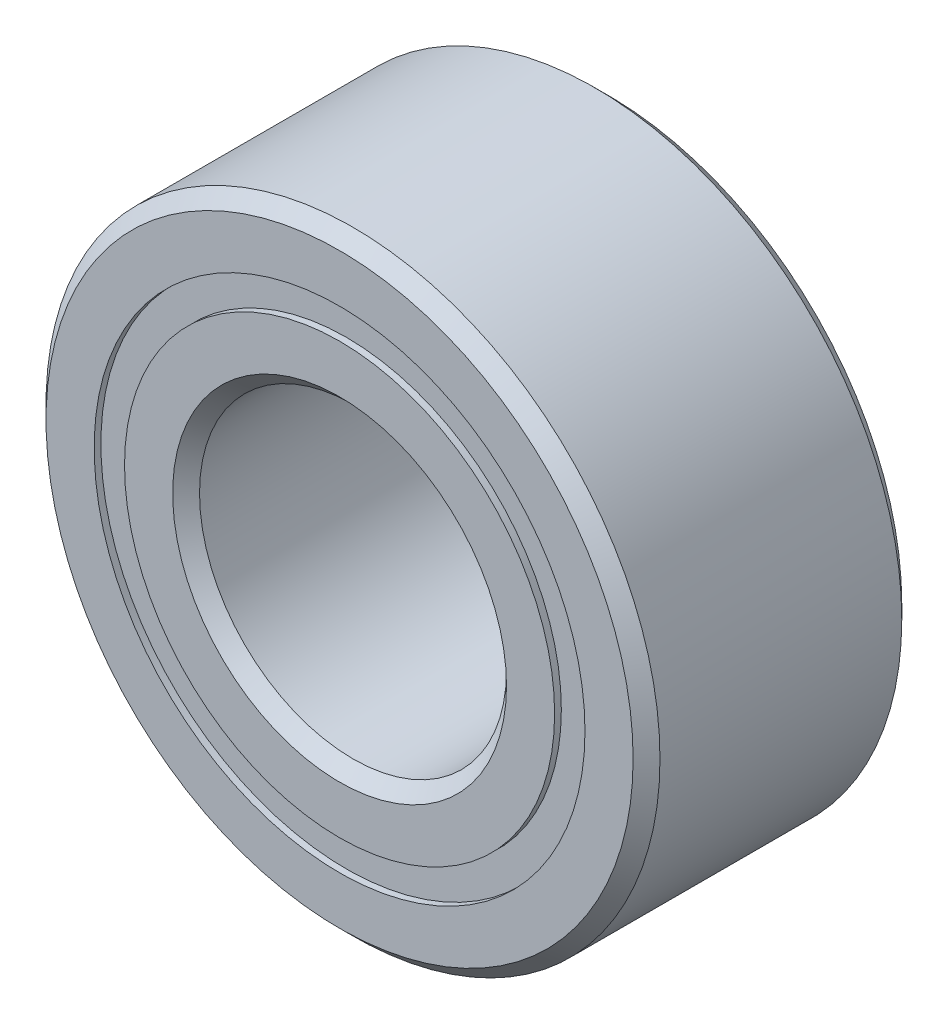
SolidWorks part; units mm, degrees
material "AISI 1020"
ref_plane "Front Plane" through (0, 0, 0) normal (0, 0, 1) x (1, 0, 0)
ref_plane "Top Plane" through (0, 0, 0) normal (0, 1, 0) x (1, 0, 0)
ref_plane "Right Plane" through (0, 0, 0) normal (1, 0, 0) x (0, 0, -1)
sketch "Sketch1" plane through (0, 0, 0) normal (1, 0, 0) x (0, 0, -1)
  line L0 (-1.3894, 0) -> (1.3894, 0) construction
  line L1 (0, 3.175) -> (0, -3.175) construction
  line L2 (1.2504, 3.175) -> (-1.2504, 3.175)
  line L3 (-1.2504, 3.175) -> (-1.3894, 3.0361)
  line L4 (-1.3894, 3.0361) -> (-1.3894, 2.5382)
  line L5 (-1.3894, 2.5382) -> (-0.6175, 2.5382)
  line L6 (1.3894, 2.5382) -> (0.6175, 2.5382)
  line L7 (1.3894, 3.0361) -> (1.3894, 2.5382)
  line L8 (1.2504, 3.175) -> (1.3894, 3.0361)
  line L9 (0, 3.175) -> (0, 2.3813) construction
  line L10 (0, 2.3813) -> (0, 1.5875) construction
  arc A0 (-0.6175, 2.5382) -> (0.6175, 2.5382) centre (0, 2.3813) cw
  point P14 (0, 1.5875)
  dimension "D3" = 1.235
  dimension "D1" = 45
  dimension "Width" = 2.7788
  dimension "OD" = 6.35
  dimension "D2" = 0.1389
  dimension "Shaft Dia" = 3.175
  dimension "D4" = 0.157
revolve "Revolve1" add sketch "Sketch1" angle 360 about L0
sketch "Sketch3" plane through (0, 0, 0) normal (1, 0, 0) x (0, 0, -1)
  line L0 (-0.6175, 2.2243) -> (-1.3894, 2.2243)
  line L1 (-1.3894, 3.0361) -> (-1.3894, 2.5382) construction
  line L2 (-1.2504, 3.175) -> (-1.3894, 3.0361) construction
  line L3 (-1.3894, 2.2243) -> (-1.3894, 1.7264)
  line L5 (-1.3894, 1.7264) -> (-1.2504, 1.5875)
  line L6 (-1.2504, 1.5875) -> (1.2504, 1.5875)
  line L7 (1.2504, 3.175) -> (1.2504, -3.175) construction
  line L8 (1.2504, 1.5875) -> (1.3894, 1.7264)
  line L9 (1.3894, -3.0361) -> (1.3894, 3.0361) construction
  line L10 (1.3894, 1.7264) -> (1.3894, 2.2243)
  line L11 (1.3894, 2.2243) -> (0.6175, 2.2243)
  line L12 (0, 3.175) -> (0, -3.175) construction
  line L13 (1.2504, 3.175) -> (1.3894, 3.0361) construction
  arc A1 (0.6175, 2.2243) -> (-0.6175, 2.2243) centre (0, 2.3812) cw
  arc A2 (0.6175, 2.5382) -> (-0.6175, 2.5382) centre (0, 2.3813) ccw construction
revolve "Revolve3" add sketch "Sketch3" angle 360 about L0
sketch "Sketch4" plane through (0, 0, 0) normal (1, 0, 0) x (0, 0, -1)
  line L0 (-0.6371, 2.3812) -> (0.6371, 2.3812)
  arc A2 (-0.6371, 2.3812) -> (0.6371, 2.3812) centre (0, 2.3813) cw
  arc A3 (0.6175, 2.5382) -> (-0.6175, 2.5382) centre (0, 2.3813) ccw construction
revolve "Revolve4" add sketch "Sketch4" angle 360 about L0
ref_axis "Axis1" through (0, 0, -1.3894) along (0, 0, 1)
pattern_circular "CirPattern1" count 10 every 36 about axis through (0, 0, -1.3894) along (0, 0, 1) of bodies 104
sketch "Sketch5" plane through (0, 0, 0) normal (1, 0, 0) x (0, 0, -1)
  line L0 (-1.3894, 2.5382) -> (-0.6175, 2.5382) construction
  line L1 (-1.3199, 2.5382) -> (-0.6371, 2.5382)
  line L2 (-1.3199, 2.5382) -> (-1.3199, 2.2243)
  line L3 (-1.3199, 2.2243) -> (-0.6371, 2.2243)
  line L4 (-0.6371, 2.5382) -> (-0.6371, 2.2243)
  line L5 (-0.6175, 2.2243) -> (-1.3894, 2.2243) construction
  line L6 (1.3894, 2.5382) -> (0.6175, 2.5382) construction
  line L7 (1.3199, 2.5382) -> (0.6371, 2.5382)
  line L8 (1.3199, 2.5382) -> (1.3199, 2.2243)
  line L9 (1.3199, 2.2243) -> (0.6371, 2.2243)
  line L10 (0.6371, 2.5382) -> (0.6371, 2.2243)
  line L11 (1.3894, 2.2243) -> (0.6175, 2.2243) construction
  line L12 (-1.2504, 3.175) -> (-1.3894, 3.0361) construction
  point P18 (-1.3199, 3.1055)
revolve "Revolve5" add sketch "Sketch5" angle 360 about L0
equation "\"D2@Sketch1\" = \"Width@Sketch1\"*.05"
equation "\"D3@Sketch1\" = \"Width@Sketch1\"/2.25"
equation "\"D4@Sketch1\" = (((\"OD@Sketch1\"-\"Width@Sketch1\")/2)/3.25)/3.5"
equation "\"D2@CirPattern1\" = 360/\"Balls@CirPattern1\""
